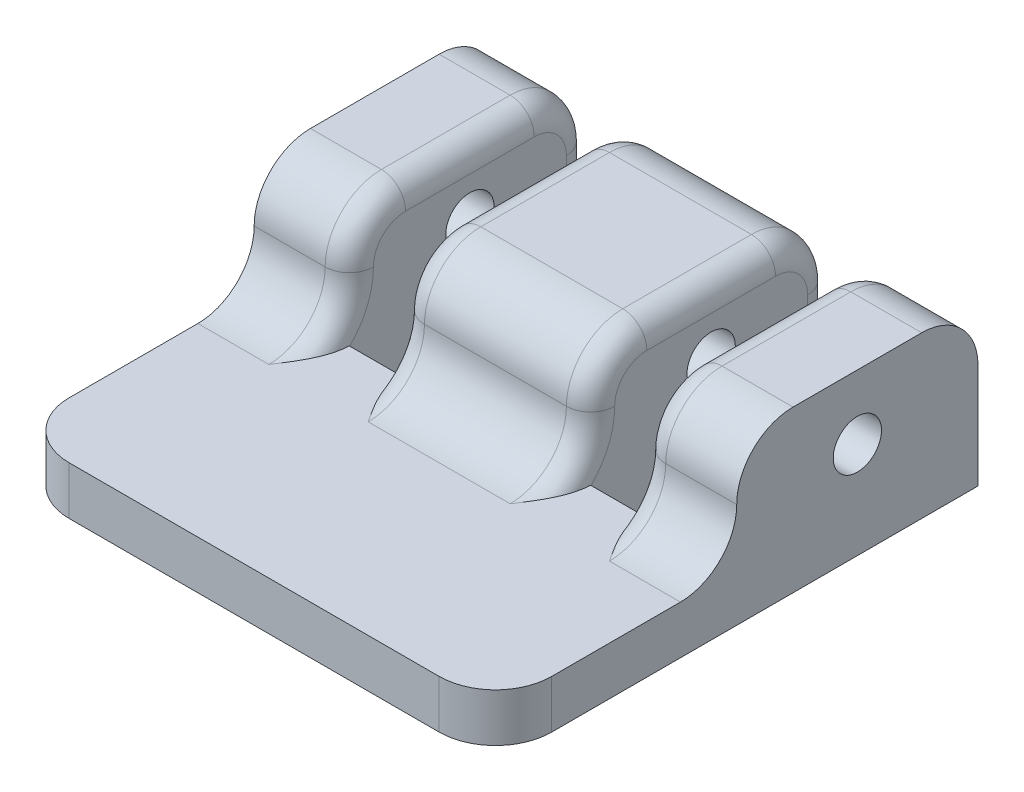
SolidWorks part; units mm, degrees
ref_plane "Front Plane" through (0, 0, 0) normal (0, 0, 1) x (1, 0, 0)
ref_plane "Top Plane" through (0, 0, 0) normal (0, 1, 0) x (1, 0, 0)
ref_plane "Right Plane" through (0, 0, 0) normal (1, 0, 0) x (0, 0, -1)
sketch "Sketch1" plane through (0, 0, 0) normal (1, 0, 0) x (0, 0, -1)
  line L0 (0, 0) -> (-30, 0)
  line L1 (-30, 0) -> (-30, 3)
  line L2 (-30, 3) -> (-15, 3)
  line L3 (-15, 3) -> (-15, 10)
  line L4 (-15, 10) -> (0, 10)
  line L5 (0, 10) -> (0, 0)
  dimension "D1" = 3
  dimension "D2" = 30
  dimension "D3" = 15
  dimension "D4" = 10
extrude "Boss-Extrude1" add sketch "Sketch1" along normal blind 30
sketch "Sketch2" plane through (30, 0, 0) normal (1, 0, 0) x (0, 0, -1)
  line L0 (-7.5, 10) -> (-7.5, 0) construction
  line L1 (0, 10) -> (-15, 10) construction
  line L2 (-30, 0) -> (0, 0) construction
  circle A0 centre (-7.5, 6) radius 1.5
  dimension "D1" = 3
  dimension "D2" = 6
extrude "Cut-Extrude1" cut sketch "Sketch2" against normal through all
sketch "Sketch3" plane through (0, 0, 0) normal (0, 0, -1) x (-1, 0, 0)
  line L0 (-15, 10) -> (-15, 0) construction
  line L1 (-30, 10) -> (0, 10) construction
  line L2 (-30, 0) -> (0, 0) construction
  line L3 (-15, 5) -> (-30, 5) construction
  line L8 (-30, 0) -> (-30, 10) construction
  line L9 (-5.9125, 0) -> (-9.0875, 0)
  line L10 (-24.0875, 10) -> (-20.9125, 10)
  line L11 (-24.0875, 10) -> (-24.0875, 0)
  line L12 (-24.0875, 0) -> (-20.9125, 0)
  line L13 (-20.9125, 10) -> (-20.9125, 0)
  line L14 (-24.0875, 10) -> (-20.9125, 0) construction
  line L15 (-24.0875, 0) -> (-20.9125, 10) construction
  line L16 (-9.0875, 10) -> (-9.0875, 0)
  line L17 (-5.9125, 10) -> (-9.0875, 10)
  line L18 (-5.9125, 10) -> (-5.9125, 0)
  point P10 (-22.5, 5)
  dimension "D1" = 3.175
extrude "Cut-Extrude2" cut sketch "Sketch3" against normal up to surface (15 mm away) up to face at (15, 6.5, 15)
fillet "Fillet1" radius 3.5 11 edges at (0, 1.5, 30) (30, 1.5, 30) (15, 10, 0) (15, 3, 15) (15, 10, 15) (2.9563, 10, 0) (27.0437, 10, 0) (2.9563, 10, 15) (27.0437, 10, 15) (27.0437, 3, 15) (2.9562, 3, 15)
fillet "Fillet2" radius 1.5 20 edges at (5.9125, 4.0251, 16.0251) (5.9125, 8.9749, 13.9749) (5.9125, 3.25, 0) (5.9125, 8.9749, 1.0251) (9.0875, 4.0251, 16.0251) (9.0875, 8.9749, 13.9749) (9.0875, 3.25, 0) (9.0875, 8.9749, 1.0251) (24.0875, 4.0251, 16.0251) (24.0875, 8.9749, 13.9749) (24.0875, 3.25, 0) (24.0875, 8.9749, 1.0251) (20.9125, 4.0251, 16.0251) (20.9125, 8.9749, 13.9749) (20.9125, 3.25, 0) (20.9125, 8.9749, 1.0251) (5.9125, 10, 7.5) (9.0875, 10, 7.5) (24.0875, 10, 7.5) (20.9125, 10, 7.5)
